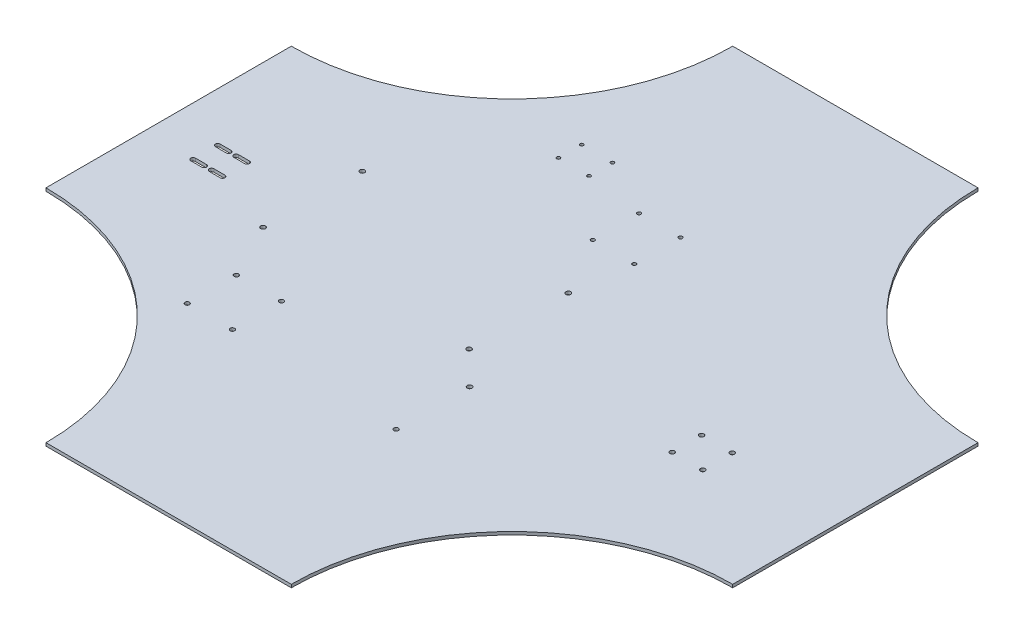
SolidWorks part; units mm, degrees
material "6061 Alloy"
ref_plane "Front Plane" through (0, 0, 0) normal (0, 0, 1) x (1, 0, 0)
ref_plane "Top Plane" through (0, 0, 0) normal (0, 1, 0) x (1, 0, 0)
ref_plane "Right Plane" through (0, 0, 0) normal (1, 0, 0) x (0, 0, -1)
sketch "Sketch1" plane through (0, 0, 0) normal (0, 1, 0) x (1, 0, 0)
  line L9 (-127, -355.6) -> (127, -355.6)
  line L10 (-355.6, -127) -> (-355.6, 127)
  line L11 (-127, 355.6) -> (127, 355.6)
  line L12 (355.6, -127) -> (355.6, 127)
  line L13 (-193.9554, -193.9554) -> (193.9554, 193.9554) construction
  line L14 (-193.9554, 193.9554) -> (193.9554, -193.9554) construction
  arc A8 (-355.6, 127) -> (-127, 355.6) centre (-355.6, 355.6) ccw
  arc A9 (127, 355.6) -> (355.6, 127) centre (355.6, 355.6) ccw
  arc A10 (355.6, -127) -> (127, -355.6) centre (355.6, -355.6) ccw
  arc A11 (-127, -355.6) -> (-355.6, -127) centre (-355.6, -355.6) ccw
  point P0 (0, 0)
  point P1 (0, 0)
  point P2 (0, 0)
  dimension "D3" = 457.2
  dimension "D4" = 457.2
  dimension "D5" = 457.2
  dimension "D6" = 457.2
  dimension "D1" = 711.2
  dimension "D2" = 711.2
extrude "Boss-Extrude1" add sketch "Sketch1" along normal blind 3.175
sketch "Sketch2" plane through (0, 3.175, 0) normal (0, 1, 0) x (1, 0, 0)
  line L0 (-304.8, 2.413) -> (-293.37, 2.413)
  line L1 (-304.8, -22.987) -> (-293.37, -22.987)
  line L2 (-293.37, -2.413) -> (-304.8, -2.413)
  line L3 (-285.75, -2.413) -> (-274.32, -2.413)
  line L4 (-285.75, -22.987) -> (-274.32, -22.987)
  line L5 (-274.32, 2.413) -> (-285.75, 2.413)
  line L6 (-293.37, -27.813) -> (-304.8, -27.813)
  line L7 (-355.6, 127) -> (-355.6, -127) construction
  line L8 (-274.32, -27.813) -> (-285.75, -27.813)
  arc A0 (-293.37, -2.413) -> (-293.37, 2.413) centre (-293.37, 0) ccw
  arc A1 (-274.32, -2.413) -> (-274.32, 2.413) centre (-274.32, 0) ccw
  arc A2 (-274.32, -27.813) -> (-274.32, -22.987) centre (-274.32, -25.4) ccw
  arc A3 (-293.37, -27.813) -> (-293.37, -22.987) centre (-293.37, -25.4) ccw
  arc A4 (-285.75, 2.413) -> (-285.75, -2.413) centre (-285.75, 0) ccw
  arc A5 (-304.8, 2.413) -> (-304.8, -2.413) centre (-304.8, 0) ccw
  arc A6 (-304.8, -22.987) -> (-304.8, -27.813) centre (-304.8, -25.4) ccw
  arc A7 (-285.75, -22.987) -> (-285.75, -27.813) centre (-285.75, -25.4) ccw
  dimension "D1" = 4.826
  dimension "D2" = 4.826
  dimension "D3" = 4.826
  dimension "D4" = 4.826
  dimension "D5" = 4.826
  dimension "D6" = 4.826
  dimension "D7" = 4.826
  dimension "D8" = 4.826
  dimension "D9" = 11.43
  dimension "D10" = 11.43
  dimension "D11" = 11.43
  dimension "D12" = 11.43
  dimension "D13" = 19.05
  dimension "D14" = 19.05
  dimension "D15" = 25.4
  dimension "D16" = 25.4
  dimension "D17" = 0
  dimension "D18" = 50.8
extrude "Cut-Extrude1" cut sketch "Sketch2" against normal through all both and the other way through all
sketch "Sketch4" plane through (0, 3.175, 0) normal (0, 1, 0) x (1, 0, 0)
  circle A0 centre (237.49, -9.4302) radius 2.413
  circle A1 centre (205.74, -9.4302) radius 2.413
  circle A2 centre (237.49, -39.9102) radius 2.413
  circle A3 centre (205.74, -39.9102) radius 2.413
extrude "Cut-Extrude2" cut sketch "Sketch4" against normal through all
sketch "Sketch5" plane through (0, 0, 0) normal (0, -1, 0) x (1, 0, 0)
  circle A0 centre (-207.7901, 50.0166) radius 2.5
  circle A1 centre (-206.624, -51.5767) radius 2.5
  circle A2 centre (8.0956, 52.4945) radius 2.478
  circle A3 centre (9.2617, -49.0988) radius 2.5
extrude "Cut-Extrude3" cut sketch "Sketch5" against normal through all
sketch "Sketch6" plane through (0, 0, 0) normal (0, -1, 0) x (1, 0, 0)
  circle A0 centre (-131.9657, 157.5947) radius 2.3218
  circle A1 centre (-131.9657, 106.7947) radius 2.3218
  circle A2 centre (-178.7006, 106.7947) radius 2.3218
  circle A3 centre (-178.7006, 157.5947) radius 2.3218
  circle A4 centre (42.2659, 162.3375) radius 2.3463
  circle A5 centre (42.2659, 86.1375) radius 2.5
  circle A6 centre (17.3717, -109.2657) radius 1.905
  circle A7 centre (-25.6811, -109.3842) radius 1.905
  circle A8 centre (-25.5498, -157.136) radius 1.905
  circle A9 centre (17.503, -157.0152) radius 1.905
  circle A10 centre (-84.8824, -188.8713) radius 1.75
  circle A11 centre (-85.0918, -164.8722) radius 1.75
  circle A12 centre (-116.8812, -189.1505) radius 1.75
  circle A13 centre (-117.0906, -165.1514) radius 1.75
extrude "Cut-Extrude4" cut sketch "Sketch6" against normal through all
